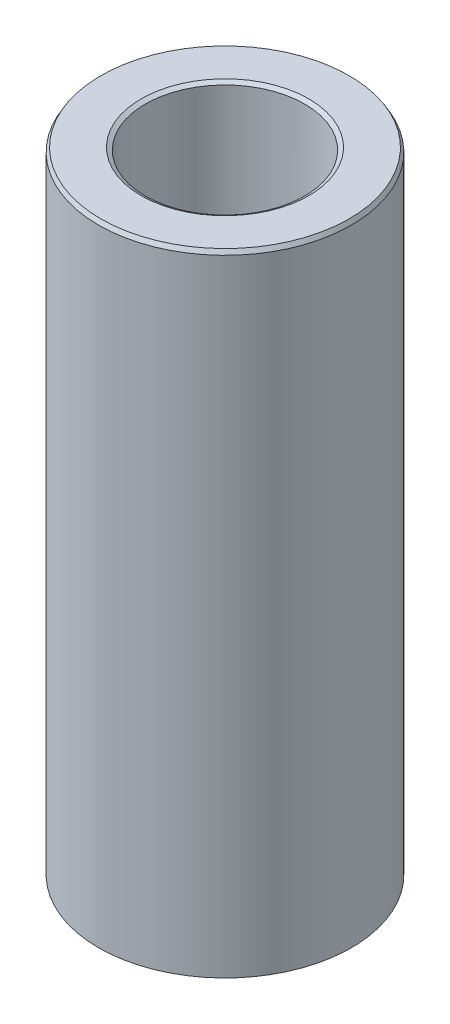
SolidWorks part; units mm, degrees
ref_plane "Front Plane" through (0, 0, 0) normal (0, 0, 1) x (1, 0, 0)
ref_plane "Top Plane" through (0, 0, 0) normal (0, 1, 0) x (1, 0, 0)
ref_plane "Right Plane" through (0, 0, 0) normal (1, 0, 0) x (0, 0, -1)
sketch "Sketch1" plane through (0, 0, 0) normal (0, 1, 0) x (1, 0, 0)
  circle A0 centre (0, 0) radius 27.5
  dimension "SLEEVE_OD" = 55
extrude "Boss-Extrude1" add sketch "Sketch1" along normal blind 137.4927
sketch "Sketch2" plane through (0, 0, 0) normal (0, 1, 0) x (1, 0, 0)
  circle A0 centre (0, 0) radius 17.3253
  dimension "BORE_D" = 34.6507
extrude "Cut-Extrude1" cut sketch "Sketch2" along normal through all
chamfer "Chamfer1" distance 0.9044 angle 30 4 edges at (0, 137.4927, 17.3253) (0, 0, 17.3253) (0, 0, 27.5) (0, 137.4927, 27.5) first distance on face at (0, 137.4927, 17.3253) first distance on face at (0, 0, 17.3253) first distance on face at (0, 137.4927, 27.5)
